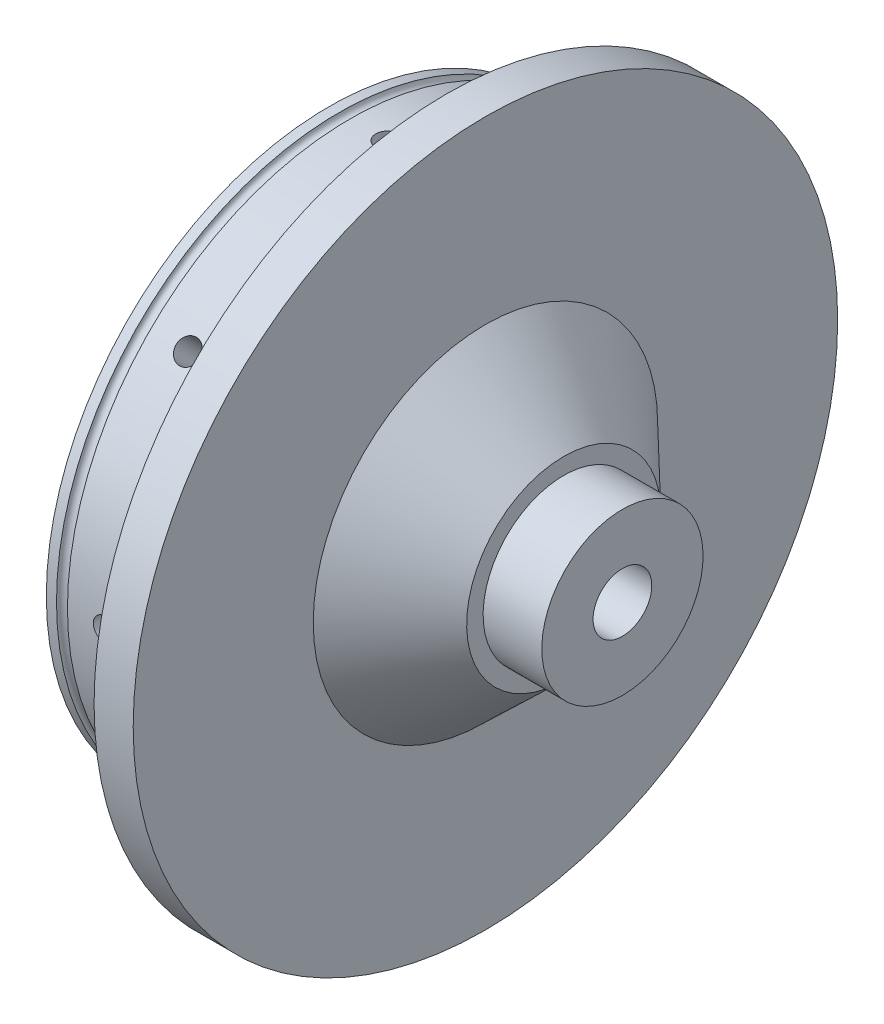
SolidWorks part; units mm, degrees
material "7075-T6 (SN)"
ref_plane "Front Plane" through (0, 0, 0) normal (0, 0, 1) x (1, 0, 0)
ref_plane "Top Plane" through (0, 0, 0) normal (0, 1, 0) x (1, 0, 0)
ref_plane "Right Plane" through (0, 0, 0) normal (1, 0, 0) x (0, 0, -1)
sketch "Sketch1" plane through (0, 0, 0) normal (1, 0, 0) x (0, 0, -1)
  circle A0 centre (0, 0) radius 57.15
  dimension "D1" = 114.3
extrude "Boss-Extrude1" add sketch "Sketch1" along normal blind 6.35
sketch "Sketch2" plane through (0, 0, 0) normal (-1, 0, 0) x (0, 0, 1)
  circle A0 centre (0, 0) radius 45.847
  dimension "D1" = 91.694
extrude "Boss-Extrude2" add sketch "Sketch2" along normal blind 19.05
sketch "Sketch3" plane through (-19.05, 0, 0) normal (-1, 0, 0) x (0, 0, 1)
  circle A0 centre (0, 0) radius 38.227
  dimension "D1" = 76.454
extrude "Cut-Extrude1" cut sketch "Sketch3" against normal blind 6.35
sketch "Sketch5" plane through (0, 0, 0) normal (0, 0, 1) x (1, 0, 0)
  line L0 (0, 45.847) -> (-19.05, 45.847) construction
  line L1 (-19.05, 45.847) -> (-19.05, -45.847) construction
  line L2 (0, 0) -> (-28.6633, 0) construction
  circle A0 centre (-16.51, 45.847) radius 0.889
  dimension "D1" = 1.778
  dimension "D2" = 2.54
revolve "Cut-Revolve1" cut sketch "Sketch5" angle 360 about L2
ref_plane "Plane1" through (0, 0, 45.847) normal (0, 0, 1) x (1, 0, 0)
sketch "Sketch6" plane through (0, 0, 45.847) normal (0, 0, 1) x (1, 0, 0)
  line L0 (0, 45.847) -> (0, -45.847) construction
  circle A0 centre (-9.525, 0) radius 1.905
  dimension "D1" = 3.81
  dimension "D2" = 9.525
extrude "Cut-Extrude3" cut sketch "Sketch6" against normal blind 6.35
pattern_circular "CirPattern1" count 8 every 45 about axis through (-19.05, 0, 0) along (1, 0, 0) of "Cut-Extrude3"
sketch "Sketch10" plane through (-12.7, 0, 0) normal (-1, 0, 0) x (0, 0, 1)
  circle A0 centre (0, 33.3375) radius 1.1303
  circle A1 centre (23.5732, 23.5732) radius 1.1303
  circle A2 centre (33.3375, 0) radius 1.1303
  circle A3 centre (23.5732, -23.5732) radius 1.1303
  circle A4 centre (0, -33.3375) radius 1.1303
  circle A5 centre (-23.5732, -23.5732) radius 1.1303
  circle A6 centre (-33.3375, 0) radius 1.1303
  circle A7 centre (-23.5732, 23.5732) radius 1.1303
  point P19 (0, 0)
  dimension "D2" = 2.2606
  dimension "D1" = 33.3375
  dimension "D3" = 8
extrude "Cut-Extrude5" cut sketch "Sketch10" against normal blind 5.08
sketch "Sketch17" plane through (0, 0, 0) normal (0, 0, 1) x (1, 0, 0)
  line L1 (6.35, -57.15) -> (6.35, 57.15) construction
  line L2 (19.05, 0) -> (6.35, 0)
  line L4 (19.05, 0) -> (19.05, 15.748)
  line L7 (19.05, 15.748) -> (6.35, 27.94)
  line L9 (6.35, 27.94) -> (6.35, 0)
  dimension "D1" = 27.94
  dimension "D2" = 15.748
  dimension "D3" = 12.7
revolve "Revolve1" add sketch "Sketch17" angle 360 about L2
sketch "Sketch18" plane through (19.05, 0, 0) normal (1, 0, 0) x (0, 0, -1)
  circle A0 centre (0, 0) radius 13.081
  dimension "D1" = 26.162
extrude "Boss-Extrude6" add sketch "Sketch18" along normal blind 9.525
sketch "Sketch19" plane through (28.575, 0, 0) normal (1, 0, 0) x (0, 0, -1)
  circle A0 centre (0, 0) radius 4.7625
  dimension "D1" = 9.525
extrude "Cut-Extrude7" cut sketch "Sketch19" against normal through all
sketch "Sketch20" plane through (0, 0, 0) normal (0, 0, 1) x (1, 0, 0)
  line L0 (19.05, 4.7625) -> (-12.7, 4.7625)
  line L1 (-12.7, 38.227) -> (-12.7, -38.227) construction
  line L2 (-12.7, 4.7625) -> (-12.7, 30.1625)
  line L3 (-2.54, 24.0665) -> (19.05, 4.7625)
  line L4 (0, 0) -> (-28.3532, 0) construction
  line L5 (-12.7, 30.1625) -> (-4.572, 30.1625)
  line L6 (-2.54, 28.1305) -> (-2.54, 24.0665)
  arc A0 (-2.54, 28.1305) -> (-4.572, 30.1625) centre (-4.572, 28.1305) ccw
  point P12 (-2.54, 30.1625)
  dimension "D5" = 2.032
  dimension "D1" = 4.7625
  dimension "D2" = 31.75
  dimension "D3" = 25.4
  dimension "D4" = 10.16
revolve "Cut-Revolve2" cut sketch "Sketch20" angle 360 about L4
